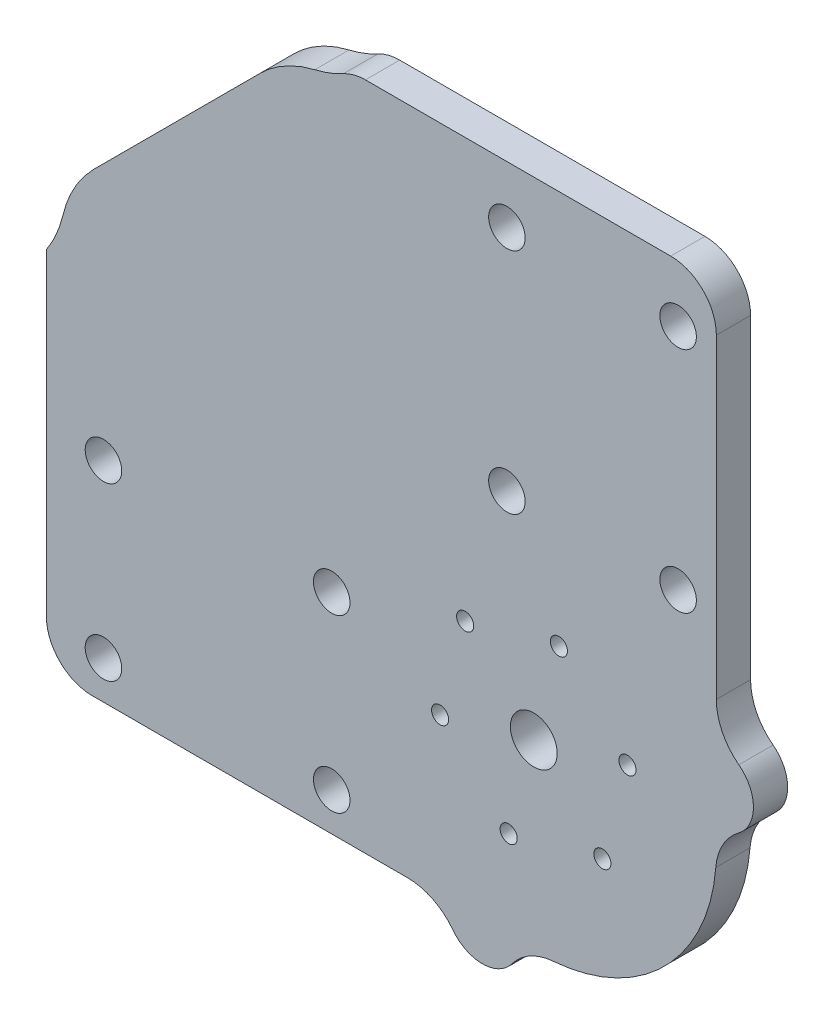
SolidWorks part; units mm, degrees
ref_plane "Front Plane" through (0, 0, 0) normal (0, 0, 1) x (1, 0, 0)
ref_plane "Top Plane" through (0, 0, 0) normal (0, 1, 0) x (1, 0, 0)
ref_plane "Right Plane" through (0, 0, 0) normal (1, 0, 0) x (0, 0, -1)
sketch "Sketch1" plane through (0, 0, 0) normal (0, 0, 1) x (1, 0, 0)
  line L5 (76.7764, -141.0656) -> (112.0043, -141.0656)
  line L6 (139.0665, -114.0034) -> (139.0665, -78.7755)
  line L7 (133.0298, -68.8657) -> (117.6434, -68.8657)
  line L8 (99.0883, -86.4845) -> (84.4854, -101.0874)
  line L9 (66.8665, -119.6426) -> (66.8665, -135.0289)
  line L10 (76.7764, -141.0656) -> (112.0043, -141.0656)
  line L11 (139.0665, -114.0034) -> (139.0665, -78.7755)
  line L12 (133.0298, -68.8657) -> (117.6434, -68.8657)
  line L13 (99.0883, -86.4845) -> (84.4854, -101.0874)
  line L14 (66.8665, -119.6426) -> (66.8665, -135.0289)
  circle A0 centre (129.0799, -131.091) radius 0.75 construction
  circle A1 centre (120.8695, -133.291) radius 0.75 construction
  circle A2 centre (114.8618, -127.2772) radius 0.75 construction
  circle A3 centre (117.0591, -119.0702) radius 0.75 construction
  circle A4 centre (125.2722, -116.8669) radius 0.75 construction
  circle A5 centre (123.0695, -125.0806) radius 2.05 construction
  circle A6 centre (131.2799, -122.8807) radius 0.75 construction
  circle A7 centre (85.3665, -122.7156) radius 1.6 construction
  circle A8 centre (85.3665, -137.7156) radius 1.6 construction
  circle A9 centre (105.3665, -137.7156) radius 1.6 construction
  circle A10 centre (105.3665, -122.7156) radius 1.6 construction
  circle A11 centre (135.7165, -87.3657) radius 1.6 construction
  circle A12 centre (120.7165, -87.3657) radius 1.6 construction
  circle A13 centre (120.7165, -107.3657) radius 1.6 construction
  circle A14 centre (135.7165, -107.3657) radius 1.6 construction
  arc A15 (66.8665, -135.0289) -> (70.9567, -141.0656) centre (73.3665, -135.0289) ccw
  arc A16 (70.9567, -141.0656) -> (76.7764, -141.0656) centre (73.8665, -140.3357) ccw
  arc A17 (115.9814, -143.0353) -> (112.0043, -141.0656) centre (112.0043, -146.0656) ccw
  arc A18 (115.9814, -143.0353) -> (121.1705, -143.0104) centre (118.5665, -141.0656) ccw
  arc A19 (124.7838, -141.0178) -> (121.1705, -143.0104) centre (125.1765, -146.0023) ccw
  arc A20 (124.7838, -141.0178) -> (139.0187, -126.7829) centre (123.5665, -125.5656) ccw
  arc A21 (141.0113, -123.1696) -> (139.0187, -126.7829) centre (144.0032, -127.1756) ccw
  arc A22 (141.0113, -123.1696) -> (141.0362, -117.9805) centre (139.0665, -120.5656) ccw
  arc A23 (139.0665, -114.0034) -> (141.0362, -117.9805) centre (144.0665, -114.0034) ccw
  arc A24 (139.0665, -78.7755) -> (139.0665, -72.9558) centre (138.3366, -75.8657) ccw
  arc A25 (139.0665, -72.9558) -> (133.0298, -68.8657) centre (133.0298, -75.3657) ccw
  arc A26 (117.6434, -68.8657) -> (111.6066, -72.9558) centre (117.6434, -75.3657) ccw
  arc A27 (111.6066, -72.9558) -> (110.6508, -78.3472) centre (112.3366, -75.8657) ccw
  arc A28 (76.3481, -112.6499) -> (70.9567, -113.6058) centre (73.8665, -114.3357) ccw
  arc A29 (70.9567, -113.6058) -> (66.8665, -119.6426) centre (73.3665, -119.6426) ccw
  arc A30 (66.8665, -135.0289) -> (70.9567, -141.0656) centre (73.3665, -135.0289) ccw
  arc A31 (70.9567, -141.0656) -> (76.7764, -141.0656) centre (73.8665, -140.3357) ccw
  arc A32 (115.9814, -143.0353) -> (112.0043, -141.0656) centre (112.0043, -146.0656) ccw
  arc A33 (115.9814, -143.0353) -> (121.1705, -143.0104) centre (118.5665, -141.0656) ccw
  arc A34 (124.7838, -141.0178) -> (121.1705, -143.0104) centre (125.1765, -146.0023) ccw
  arc A35 (124.7838, -141.0178) -> (139.0187, -126.7829) centre (123.5665, -125.5656) ccw
  arc A36 (141.0113, -123.1696) -> (139.0187, -126.7829) centre (144.0032, -127.1756) ccw
  arc A37 (141.0113, -123.1696) -> (141.0362, -117.9805) centre (139.0665, -120.5656) ccw
  arc A38 (139.0665, -114.0034) -> (141.0362, -117.9805) centre (144.0665, -114.0034) ccw
  arc A39 (139.0665, -78.7755) -> (139.0665, -72.9558) centre (138.3366, -75.8657) ccw
  arc A40 (139.0665, -72.9558) -> (133.0298, -68.8657) centre (133.0298, -75.3657) ccw
  arc A41 (117.6434, -68.8657) -> (111.6066, -72.9558) centre (117.6434, -75.3657) ccw
  arc A42 (111.6066, -72.9558) -> (110.6508, -78.3472) centre (112.3366, -75.8657) ccw
  arc A43 (76.3481, -112.6499) -> (70.9567, -113.6058) centre (73.8665, -114.3357) ccw
  arc A44 (70.9567, -113.6058) -> (66.8665, -119.6426) centre (73.3665, -119.6426) ccw
  circle A45 centre (129.0799, -131.091) radius 0.75
  circle A46 centre (120.8695, -133.291) radius 0.75
  circle A47 centre (114.8618, -127.2772) radius 0.75
  circle A48 centre (117.0591, -119.0702) radius 0.75
  circle A49 centre (125.2722, -116.8669) radius 0.75
  circle A50 centre (123.0695, -125.0806) radius 2.05
  circle A51 centre (131.2799, -122.8807) radius 0.75
  circle A52 centre (85.3665, -122.7156) radius 1.6
  circle A53 centre (85.3665, -137.7156) radius 1.6
  circle A54 centre (105.3665, -137.7156) radius 1.6
  circle A55 centre (105.3665, -122.7156) radius 1.6
  circle A56 centre (135.7165, -87.3657) radius 1.6
  circle A57 centre (120.7165, -87.3657) radius 1.6
  circle A58 centre (120.7165, -107.3657) radius 1.6
  circle A59 centre (135.7165, -107.3657) radius 1.6
  spline S4 degree 3 poles (-3101.0122, -2439.8443) (-1.7206, 228.6075) (289.5116, -337.9047) (-146.4574, 119.1891) (3322.837, 2267.7868) knots -14.095289 -14.095289 -14.095289 -14.095289 -0.386997 13.197935 13.197935 13.197935 13.197935 weights 1 1 1 1 1 only from (110.6508, -78.3472) to (103.883, -83.8181)
  spline S5 degree 3 poles (-2858.3894, -2751.2497) (3506.6091, 2149.0906) (-3593.0011, -1799.0968) (3927.9666, 1022.7216) knots -13.199206 -13.199206 -13.199206 -13.199206 13.756485 13.756485 13.756485 13.756485 weights 1 1 1 1 only from (103.883, -83.8181) to (99.0883, -86.4845)
  spline S6 degree 3 poles (-1024.7016, -3929.9201) (1797.0856, 3590.9895) (-2151.0946, -3508.6262) (2749.28, 2856.4316) knots -12.83716 -12.83716 -12.83716 -12.83716 14.082817 14.082817 14.082817 14.082817 weights 1 1 1 1 only from (84.4854, -101.0874) to (81.819, -105.8821)
  spline S7 degree 3 poles (-2563.6028, -3088.0211) (-92.3873, 170.705) (311.1047, -322.1901) (-210.9782, 33.3832) (2730.968, 2861.3459) knots -12.742254 -12.742254 -12.742254 -12.742254 0.957761 14.534488 14.534488 14.534488 14.534488 weights 1 1 1 1 1 only from (81.819, -105.8821) to (76.3481, -112.6499)
  spline S8 degree 3 poles (110.6508, -78.3472) (109.9191, -79.8982) (107.9253, -82.272) (105.1354, -83.5253) (103.883, -83.8181) knots -0.902992 -0.902992 -0.902992 -0.902992 -0.386997 0 0 0 0 weights 1 1 1 1 1
  spline S9 degree 3 poles (103.883, -83.8181) (102.0791, -84.2398) (100.3982, -85.1746) (99.0883, -86.4845) knots 0 0 0 0 0.557223 0.557223 0.557223 0.557223 weights 1 1 1 1
  spline S10 degree 3 poles (84.4854, -101.0874) (83.1754, -102.3974) (82.2407, -104.0783) (81.819, -105.8821) knots 0.344558 0.344558 0.344558 0.344558 0.901043 0.901043 0.901043 0.901043 weights 1 1 1 1
  spline S11 degree 3 poles (81.819, -105.8821) (81.4286, -107.5521) (79.9765, -110.291) (77.5113, -112.1011) (76.3481, -112.6499) knots 0.442078 0.442078 0.442078 0.442078 0.957761 1.344523 1.344523 1.344523 1.344523 weights 1 1 1 1 1
  dimension "D1" = 0
extrude "Boss-Extrude1" add sketch "Sketch1" along normal blind 3
sketch "Sketch2" plane through (0, 0, 0) normal (0, 0, -1) x (-1, 0, 0)
  line L0 (-139.0665, -82.3657) -> (-107.2064, -82.3657)
  line L1 (-139.0665, -114.0034) -> (-139.0665, -78.7755) construction
  line L2 (-134.5267, -136.5258) -> (-91.7868, -93.786) construction
  line L3 (-99.0883, -86.4845) -> (-84.4854, -101.0874) construction
  line L4 (-139.0665, -82.3657) -> (-151.0772, -66.544)
  line L5 (-151.0772, -66.544) -> (-134.5267, -61.3028)
  line L7 (-134.5267, -61.3028) -> (-105.4893, -66.544)
  line L8 (-105.4893, -66.544) -> (-107.2064, -82.3657)
  line L9 (-64.5448, -107.4885) -> (-80.3666, -109.2056)
  line L10 (-59.3038, -136.5259) -> (-64.5448, -107.4885)
  line L11 (-64.5449, -153.0764) -> (-59.3038, -136.5259)
  line L12 (-80.3666, -141.0657) -> (-64.5449, -153.0764)
  line L13 (-80.3666, -141.0657) -> (-80.3666, -109.2056)
  circle A0 centre (-135.7165, -87.3657) radius 1.6 construction
  arc A1 (-139.0187, -126.7829) -> (-124.7838, -141.0178) centre (-123.5665, -125.5656) ccw construction
  spline S0 degree 3 poles (-110.6508, -78.3472) (-109.9191, -79.8982) (-107.9253, -82.272) (-105.1354, -83.5253) (-103.883, -83.8181) knots -0.902992 -0.902992 -0.902992 -0.902992 -0.386997 0 0 0 0 weights 1 1 1 1 1 construction
  dimension "D1" = 5
extrude "Cut-Extrude2" cut sketch "Sketch2" against normal up to surface (3 mm away) up to face at (122.3165, -107.3657, 3)
fillet "Fillet1" radius 4 4 edges at (80.3666, -141.0656, 1.5) (80.3666, -109.2056, 1.5) (107.2064, -82.3657, 1.5) (139.0665, -82.3657, 1.5)
